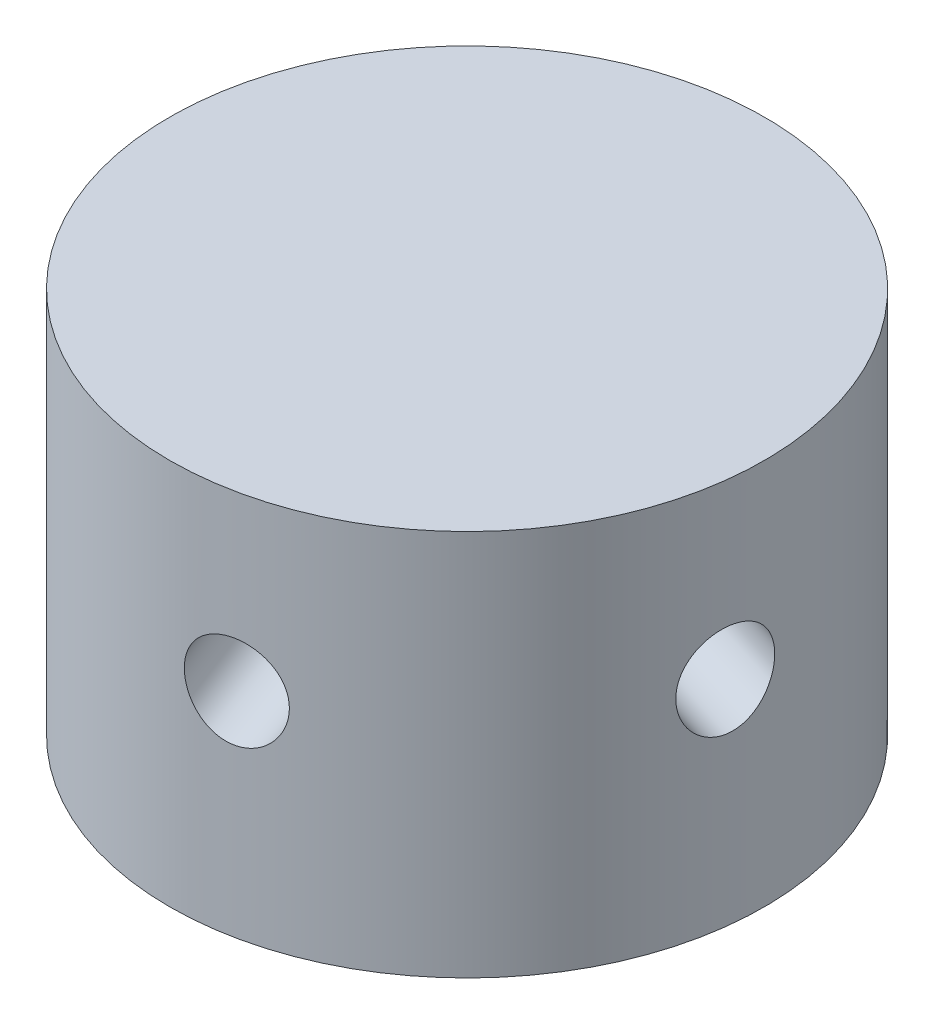
SolidWorks part; units mm, degrees
ref_plane "Front Plane" through (0, 0, 0) normal (0, 0, 1) x (1, 0, 0)
ref_plane "Top Plane" through (0, 0, 0) normal (0, 1, 0) x (1, 0, 0)
ref_plane "Right Plane" through (0, 0, 0) normal (1, 0, 0) x (0, 0, -1)
sketch "Sketch1" plane through (0, 0, 0) normal (0, 1, 0) x (1, 0, 0)
  circle A0 centre (0, 0) radius 10
  dimension "D1" = 20
extrude "Boss-Extrude1" add sketch "Sketch1" along normal blind 3 and the other way blind 10
ref_axis "5hubaxis" through (0, 5.5, 0) along (0, -1, 0)
ref_plane "holeplane" through (-3.3529, -1.0931, 1.8877) normal (0.8382, 0.2733, -0.4719) x (-0.4487, -0.1463, -0.8816)
sketch "Sketch4" plane through (-3.3529, -1.0931, 1.8877) normal (0.8382, 0.2733, -0.4719) x (-0.4487, -0.1463, -0.8816)
  circle A0 centre (0, 0) radius 1.5 construction
  circle A1 centre (0, 0) radius 1.5
extrude "hole" cut sketch "Sketch4" against normal through all
pattern_circular "holecir" count 5 over 360 about axis through (0, 5.5, 0) along (0, -1, 0) of "hole"
sketch "Sketch5" plane through (0, -10, 0) normal (0, -1, 0) x (1, 0, 0)
  line L0 (-10, 0) -> (10, 0) construction
  circle A0 centre (0, 0) radius 10 construction
  text T0 "5"
extrude "Boss-Extrude2" [suppressed] add sketch "Sketch5" along normal blind 1
ref_plane "Plane1" through (0, -5, 0) normal (0, -1, 0) x (-1, 0, 0)
sketch "Sketch6" plane through (0, -5, 0) normal (0, -1, 0) x (-1, 0, 0)
  circle A0 centre (0, 0) radius 3.5
  dimension "D1" = 7
extrude "bearinghole" cut sketch "Sketch6" along normal blind 2.5
sketch "Sketch7" plane through (0, -5, 0) normal (0, -1, 0) x (-1, 0, 0)
  circle A0 centre (0, 0) radius 2
  dimension "D1" = 4
extrude "shafthole" cut sketch "Sketch7" along normal through all
sketch "Sketch8" plane through (0, -10, 0) normal (0, -1, 0) x (1, 0, 0)
  line L0 (-9.648, 2.6298) -> (9.648, 2.6298) construction
  circle A1 centre (0, 0) radius 10 construction
  text T0 "5-axis"
extrude "Boss-Extrude3" add sketch "Sketch8" along normal blind 1
